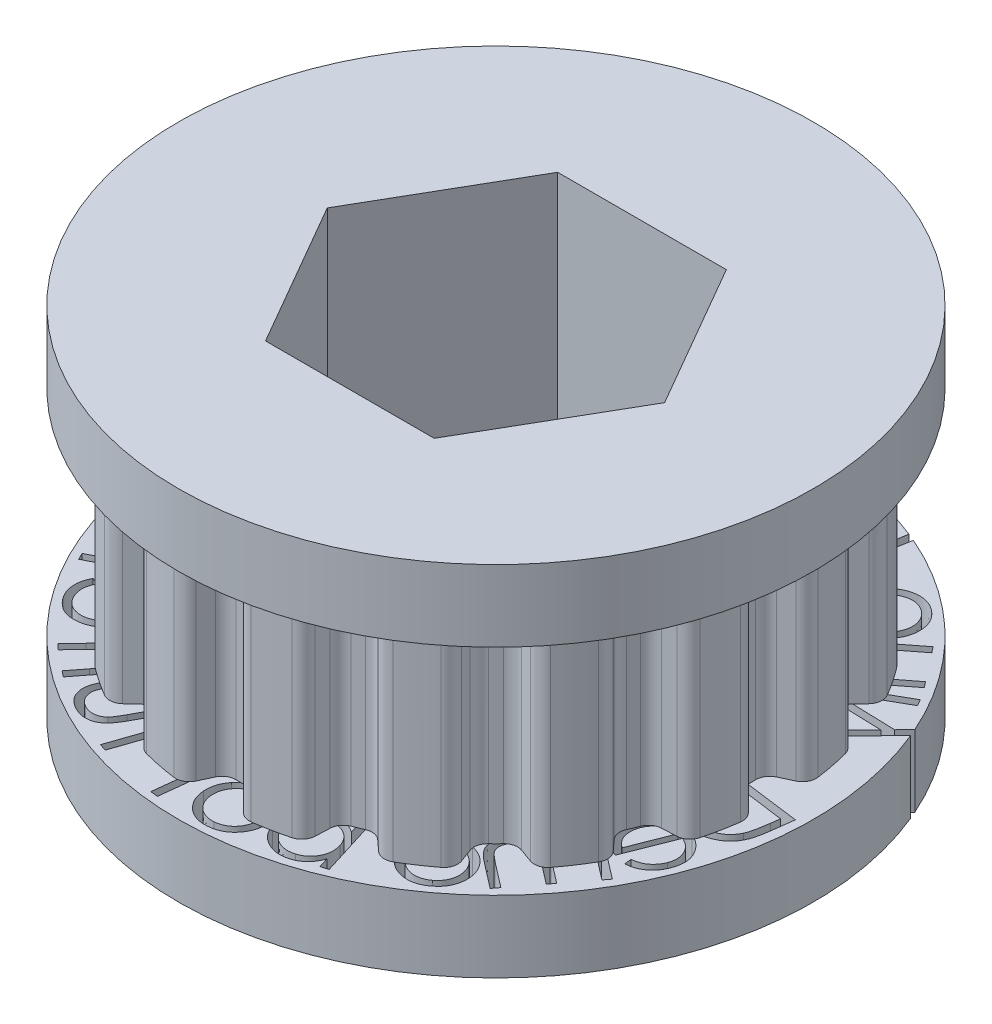
SolidWorks part; units mm, degrees
material "ABS"
ref_plane "Front Plane" through (0, 0, 0) normal (0, 0, 1) x (1, 0, 0)
ref_plane "Top Plane" through (0, 0, 0) normal (0, 1, 0) x (1, 0, 0)
ref_plane "Right Plane" through (0, 0, 0) normal (1, 0, 0) x (0, 0, -1)
sketch "Sketch1" plane through (0, 0, 0) normal (0, 1, 0) x (1, 0, 0)
  line L0 (0, 0) -> (0, 12.9361) construction
  circle A0 centre (0, 0) radius 12.9361
  point P6 (0, 210.65)
  dimension "D1" = 25.8722
extrude "Boss-Extrude1" add sketch "Sketch1" along normal blind 9.525
sketch "Sketch2" plane through (0, 9.525, 0) normal (0, 1, 0) x (1, 0, 0)
  line L0 (0, 0) -> (0, 12.9361) construction
  line L2 (-0.8063, 11.6316) -> (-1.0802, 12.2189)
  line L3 (0.8063, 11.6316) -> (1.0802, 12.2189)
  line L4 (0, 0) -> (2.4742, 12.4384) construction
  line L5 (-2.4742, 12.4384) -> (0, 0) construction
  line L6 (-2.4742, 12.4384) -> (-2.5237, 12.6875)
  line L7 (2.4742, 12.4384) -> (2.5237, 12.6875)
  circle A0 centre (0, 0) radius 12.9361 construction
  arc A1 (1.7156, 12.5655) -> (2.4742, 12.4384) centre (0, 0) cw
  arc A2 (-1.7156, 12.5655) -> (-2.4742, 12.4384) centre (0, 0) ccw
  arc A3 (2.5237, 12.6875) -> (-2.5237, 12.6875) centre (0, 0) ccw
  arc A4 (-0.2405, 11.2796) -> (0.2405, 11.2796) centre (0, 0) cw
  arc A5 (1.0802, 12.2189) -> (1.7156, 12.5655) centre (1.633, 11.9612) cw
  arc A6 (0.2405, 11.2796) -> (0.8063, 11.6316) centre (0.2535, 11.8894) ccw
  arc A7 (-0.2405, 11.2796) -> (-0.8063, 11.6316) centre (-0.2535, 11.8894) cw
  arc A8 (-1.0802, 12.2189) -> (-1.7156, 12.5655) centre (-1.633, 11.9612) ccw
  point P7 (0, 212.2279)
  point P16 (0, 11.2821)
  point P19 (0.635, 11.2642)
  point P22 (-0.635, 11.2642)
  dimension "D8" = 0.61
  dimension "D1" = 1.27
  dimension "D2" = 50
  dimension "D3" = 25
  dimension "D4" = 11.25
  dimension "D5" = 11.25
  dimension "D6" = 0.254
  dimension "D7" = 1.4
extrude "Cut-Extrude1" cut sketch "Sketch2" against normal through all
pattern_circular "CirPattern1" count 16 over 360 about axis through (0, 9.525, 0) along (0, -1, 0) of "Cut-Extrude1" reverse direction yes
sketch "Sketch3" plane through (0, 9.525, 0) normal (0, 1, 0) x (1, 0, 0)
  circle A0 centre (0, 0) radius 14.0821
  arc A1 (3.2237, 12.2656) -> (1.7156, 12.5655) centre (0, 0) ccw construction
  dimension "D1" = 1.4
extrude "Boss-Extrude2" add sketch "Sketch3" along normal blind 3.175
sketch "Sketch4" plane through (0, 0, 0) normal (0, -1, 0) x (1, 0, 0)
  circle A0 centre (0, 0) radius 14.0821 construction
  circle A1 centre (0, 0) radius 14.0821
extrude "Boss-Extrude3" add sketch "Sketch4" along normal blind 3.175
sketch "Sketch5" plane through (0, -3.175, 0) normal (0, -1, 0) x (1, 0, 0)
  line L1 (-3.7395, -6.477) -> (3.7395, -6.477)
  line L2 (3.7395, -6.477) -> (7.479, 0)
  line L3 (7.479, 0) -> (3.7395, 6.477)
  line L4 (3.7395, 6.477) -> (-3.7395, 6.477)
  line L5 (-3.7395, 6.477) -> (-7.479, 0)
  line L6 (-7.479, 0) -> (-3.7395, -6.477)
  circle A0 centre (0, 0) radius 6.477 construction
  dimension "D1" = 12.954
extrude "Cut-Extrude2" cut sketch "Sketch5" against normal through all
sketch "Sketch6" plane through (0, -3.175, 0) normal (0, -1, 0) x (1, 0, 0)
  circle A0 centre (0, 0) radius 13.7541 construction
  text T0 "Demo bot turret turn (not spin) only\r\n"
extrude "Cut-Extrude3" cut sketch "Sketch6" against normal blind 3.175
equation "\"Pitch\"= 0.2in"
equation "\"Number of Teeth\"= 16"
equation "\"Flank Angle\"= 50deg"
equation "\"Tooth bottom width\"= 1.27mm"
equation "\"Tooth height\"= 1.4mm"
equation "\"Fillet Radius\"= 0.61mm"
equation "\"Pitch zone\"= 0.254mm"
equation "\"D1@Sketch1\"=\"Pitch\" * \"Number of Teeth\" / pi"
equation "\"Width\"= 0.375in"
equation "\"D1@Boss-Extrude1\"=\"Width\""
equation "\"D1@Sketch2\"=\"Tooth bottom width\""
equation "\"D2@Sketch2\"=\"Flank Angle\""
equation "\"D3@Sketch2\"=\"Flank Angle\"/2"
equation "\"D4@Sketch2\"=180 / \"Number of Teeth\""
equation "\"D5@Sketch2\"= 180 / \"Number of Teeth\""
equation "\"D6@Sketch2\"=\"Pitch zone\""
equation "\"D7@Sketch2\"=\"Tooth height\""
equation "\"D1@CirPattern1\"=\"Number of Teeth\""
equation "\"D1@Sketch3\"=\"Tooth height\""
